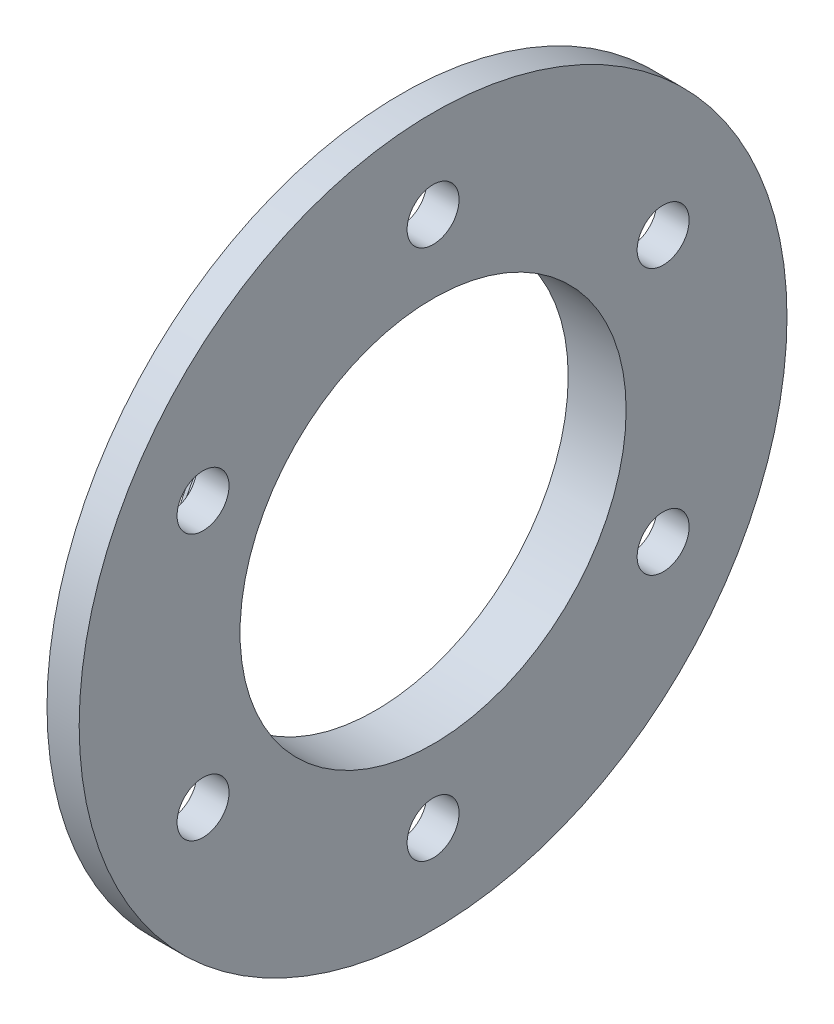
SolidWorks part; units mm, degrees
material "6061-T6 (SS)"
ref_plane "Front Plane" through (0, 0, 0) normal (0, 0, 1) x (1, 0, 0)
ref_plane "Top Plane" through (0, 0, 0) normal (0, 1, 0) x (1, 0, 0)
ref_plane "Right Plane" through (0, 0, 0) normal (1, 0, 0) x (0, 0, -1)
sketch "Sketch1" plane through (0, 0, 0) normal (1, 0, 0) x (0, 0, -1)
  line L0 (0, 0) -> (0, 20.64) construction
  arc A0 (-1.6237, 23.2194) -> (1.6237, -23.2194) centre (0, 0) ccw construction
  arc A1 (1.0588, 18.9205) -> (-1.0588, 22.3595) centre (0, 20.64) ccw construction
  circle A2 centre (0, 0) radius 27.5
  circle A3 centre (0, 20.64) radius 2.0193
  circle A4 centre (17.8748, 10.32) radius 2.0193
  circle A5 centre (17.8748, -10.32) radius 2.0193
  circle A6 centre (0, -20.64) radius 2.0193
  circle A7 centre (-17.8748, -10.32) radius 2.0193
  circle A8 centre (-17.8748, 10.32) radius 2.0193
  circle A9 centre (0, 0) radius 17.46 construction
  point P21 (0, 0)
  dimension "D1" = 23.2761
  dimension "D2" = 2.0193
  dimension "D3" = 20.64
  dimension "D5" = 34.92
  dimension "D6" = 55
  dimension "D4" = 6
extrude "Boss-Extrude1" add sketch "Sketch1" along normal blind 2.5
sketch "Sketch2" plane through (0, 0, 0) normal (-1, 0, 0) x (0, 0, 1)
  circle A0 centre (0, 0) radius 17.46 construction
  circle A1 centre (0, 0) radius 17.46
extrude "Boss-Extrude2" add sketch "Sketch2" along normal blind 2
chamfer "Chamfer5" distance 1 angle 45 1 edges at (-2, 0, 17.46)
sketch "Sketch6" plane through (-2, 0, 0) normal (1, 0, 0) x (0, 0, -1)
  line L0 (0, 11.1803) -> (0, -11.1803) construction
  line L5 (-10, -11.1803) -> (10, 11.1803) construction
  line L6 (-10, 11.1803) -> (10, -11.1803) construction
  circle A1 centre (0, 0) radius 15
  dimension "D1" = 30
  dimension "D2" = 20
extrude "Cut-Extrude1" cut sketch "Sketch6" along normal blind 10
